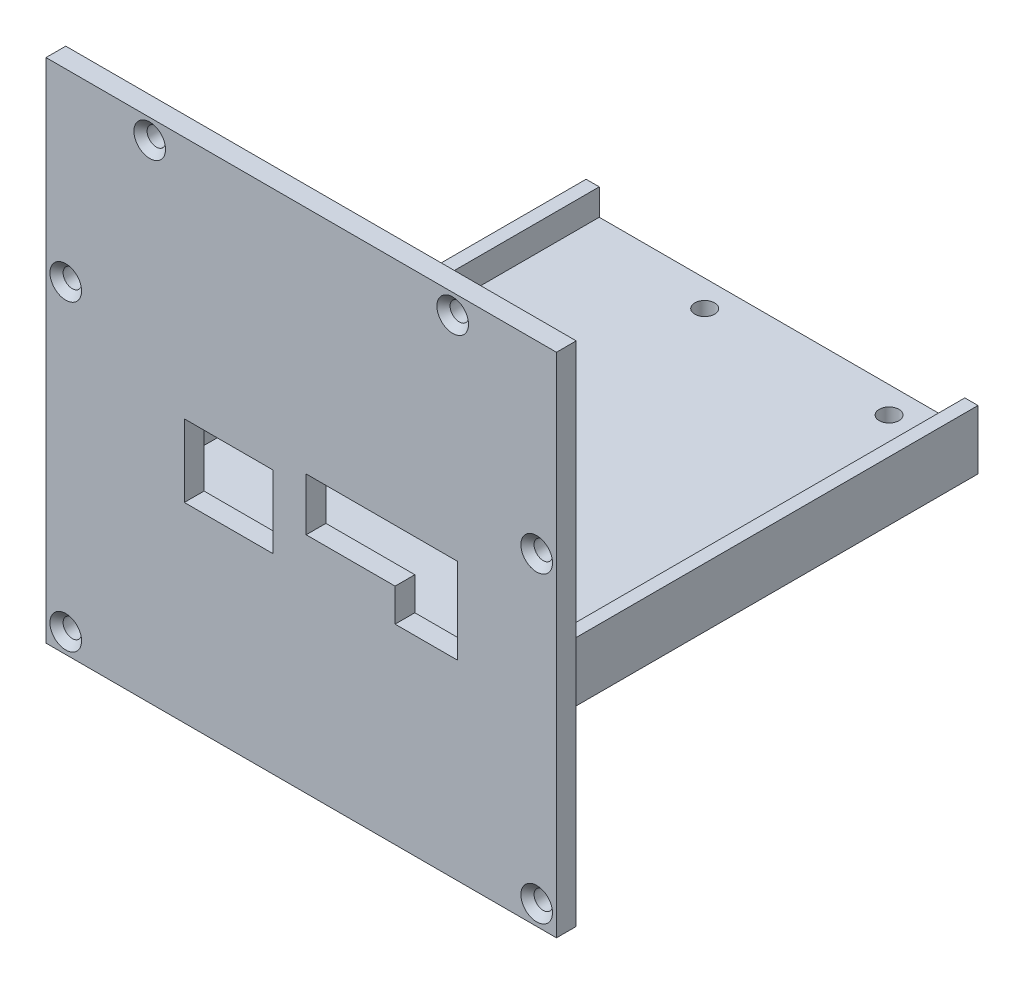
SolidWorks part; units mm, degrees
ref_plane "Płaszczyzna przednia" through (0, 0, 0) normal (0, 0, 1) x (1, 0, 0)
ref_plane "Płaszczyzna górna" through (0, 0, 0) normal (0, 1, 0) x (1, 0, 0)
ref_plane "Płaszczyzna prawa" through (0, 0, 0) normal (1, 0, 0) x (0, 0, -1)
sketch "Szkic1" plane through (0, 0, 0) normal (0, 0, 1) x (1, 0, 0)
  line L0 (14.6708, -41.7555) -> (14.6708, -118.7555) construction
  line L1 (-3.0792, -78.7555) -> (10.4208, -78.7555)
  line L2 (-3.0792, -78.7555) -> (-3.0792, -89.7555)
  line L3 (-3.0792, -89.7555) -> (10.4208, -89.7555)
  line L4 (-24.0792, -118.7555) -> (53.4208, -118.7555)
  line L5 (53.4208, -118.7555) -> (53.4208, -41.7555)
  line L6 (53.4208, -41.7555) -> (-24.0792, -41.7555)
  line L7 (-24.0792, -41.7555) -> (-24.0792, -118.7555)
  line L8 (10.4208, -78.7555) -> (10.4208, -89.7555)
  line L9 (29.4208, -76.7555) -> (38.4208, -76.7555)
  line L10 (28.9208, -84.7555) -> (28.9208, -89.7555)
  line L11 (28.9208, -89.7555) -> (38.4208, -89.7555)
  line L12 (38.4208, -76.7555) -> (38.4208, -89.7555)
  line L13 (-13.0792, -93.7555) -> (42.4208, -93.7555)
  line L14 (-13.0792, -93.7555) -> (-13.0792, -89.7555)
  line L15 (42.4208, -89.7555) -> (42.4208, -93.7555)
  line L16 (-15.0792, -98.7555) -> (-15.0792, -89.7555)
  line L17 (-15.0792, -98.7555) -> (44.4208, -98.7555)
  line L18 (44.4208, -89.7555) -> (44.4208, -98.7555)
  line L19 (-13.0792, -89.7555) -> (-15.0792, -89.7555)
  line L20 (42.4208, -89.7555) -> (44.4208, -89.7555)
  line L21 (-3.0792, -84.2555) -> (-50.0911, -84.2555) construction
  line L22 (-50.0911, -84.2555) -> (82.1697, -84.2555) construction
  line L24 (15.4208, -76.7555) -> (29.4208, -76.7555)
  line L25 (15.4208, -76.7555) -> (15.4208, -91.7555)
  line L29 (15.4208, -91.7555) -> (15.4208, -84.7555)
  line L30 (15.4208, -84.7555) -> (28.9208, -84.7555)
  line L31 (15.4208, -76.7555) -> (15.4208, -91.7555)
  line L33 (38.4208, -91.7555) -> (38.4208, -76.7555)
  dimension "D12" = 4
  dimension "D1" = 9
  dimension "D2" = 13.5
  dimension "D3" = 13
  dimension "D4" = 5
  dimension "D5" = 10
  dimension "D6" = 23
  dimension "D7" = 20
  dimension "D8" = 11
  dimension "D9" = 5
  dimension "D10" = 2
  dimension "D11" = 15
  dimension "D15" = 5
  dimension "D16" = 21
  dimension "D17" = 77
  dimension "D18" = 77.5
extrude "Dodanie-wyciągnięcie1" add sketch "Szkic1" along normal blind 3 contours L4 L1 L3 L9 L12 L11 L15 L20 L18 L17 L16 L19 L14 | L17 L18 L20 L15 L13 L14 L19 L16 region at (14.3821, -79.125, 0)
extrude "Dodanie-wyciągnięcie3" add sketch "Szkic1<5>" against normal blind 70 contours L20 L15 L13 L14 L19 L16 L17 L18 region at (14.6708, -96.0259, 0)
sketch "Szkic1<5>" plane through (0, 0, 0) normal (0, 0, 1) x (1, 0, 0) same geometry as "Szkic1"
sketch "Szkic2" plane through (0, 0, 3) normal (0, 0, 1) x (1, 0, 0)
  line L0 (-11.3292, -41.7555) -> (-5.3292, -41.7555)
  line L1 (-11.3292, -47.7555) -> (-5.3292, -47.7555)
  line L2 (-5.3292, -47.7555) -> (-5.3292, -41.7555)
  line L3 (14.6708, -70.3917) -> (14.6708, -64.3917) construction
  line L4 (-11.3292, -41.7555) -> (-5.3292, -41.7555)
  line L5 (-11.3292, -41.7555) -> (-11.3292, -47.7555)
  line L6 (40.6708, -41.7555) -> (40.6708, -47.7555)
  line L7 (40.6708, -47.7555) -> (34.6708, -47.7555)
  line L8 (34.6708, -47.7555) -> (34.6708, -41.7555)
  line L9 (40.6708, -41.7555) -> (34.6708, -41.7555)
  line L10 (-24.0792, -41.7555) -> (-24.0792, -118.7555) construction
  line L11 (53.4208, -118.7555) -> (53.4208, -41.7555) construction
  line L12 (53.4208, -41.7555) -> (-24.0792, -41.7555) construction
  circle A0 centre (-8.3292, -44.7555) radius 1.4
  circle A1 centre (37.6708, -44.7555) radius 1.4
  dimension "D1" = 2.8
  dimension "D2" = 3
  dimension "D3" = 3
  dimension "D4" = 3
  dimension "D5" = 20
extrude "Wytnij-wyciągnięcie1" cut sketch "Szkic2" against normal up to surface (3 mm away) contours A0 | A1 region at (-8.3292, -44.7555, 3) region at (37.6708, -44.7555, 3) up to face at (3.6708, -84.2555, 0)
sketch "Szkic3" plane through (0, 0, 0) normal (0, 0, -1) x (-1, 0, 0)
  line L0 (-53.4208, -66.7555) -> (-47.4208, -66.7555)
  line L1 (-53.4208, -72.7555) -> (-47.4208, -72.7555)
  line L2 (-47.4208, -72.7555) -> (-47.4208, -66.7555)
  line L3 (-14.6708, -61.974) -> (-14.6708, -55.974) construction
  line L4 (-53.4208, -66.7555) -> (-47.4208, -66.7555)
  line L5 (-53.4208, -66.7555) -> (-53.4208, -72.7555)
  line L6 (24.0792, -66.7555) -> (24.0792, -72.7555)
  line L7 (24.0792, -72.7555) -> (18.0792, -72.7555)
  line L8 (18.0792, -72.7555) -> (18.0792, -66.7555)
  line L9 (24.0792, -66.7555) -> (18.0792, -66.7555)
  line L10 (-53.4208, -112.7555) -> (-47.4208, -112.7555)
  line L11 (-53.4208, -118.7555) -> (-47.4208, -118.7555)
  line L12 (-47.4208, -118.7555) -> (-47.4208, -112.7555)
  line L13 (-14.6708, -81.1098) -> (-14.6708, -75.1098) construction
  line L14 (-53.4208, -112.7555) -> (-47.4208, -112.7555)
  line L15 (-53.4208, -112.7555) -> (-53.4208, -118.7555)
  line L16 (24.0792, -112.7555) -> (24.0792, -118.7555)
  line L17 (24.0792, -118.7555) -> (18.0792, -118.7555)
  line L18 (18.0792, -118.7555) -> (18.0792, -112.7555)
  line L19 (24.0792, -112.7555) -> (18.0792, -112.7555)
  line L20 (-53.4208, -118.7555) -> (-53.4208, -41.7555) construction
  line L21 (24.0792, -41.7555) -> (24.0792, -118.7555) construction
  line L22 (24.0792, -118.7555) -> (-53.4208, -118.7555) construction
  circle A0 centre (-50.4208, -69.7555) radius 1.4
  circle A1 centre (21.0792, -69.7555) radius 1.4
  circle A2 centre (-50.4208, -115.7555) radius 1.4
  circle A3 centre (21.0792, -115.7555) radius 1.4
  dimension "D1" = 2.8
  dimension "D6" = 2.8
  dimension "D2" = 3
  dimension "D3" = 3
  dimension "D4" = 3
  dimension "D5" = 40
  dimension "D7" = 3
  dimension "D8" = 3
  dimension "D9" = 3
sketch "Szkic4" plane through (0, 0, 3) normal (0, 0, 1) x (1, 0, 0)
  line L0 (53.4208, -66.7555) -> (47.4208, -66.7555) construction
  line L1 (47.4208, -72.7555) -> (47.4208, -66.7555) construction
  line L2 (53.4208, -72.7555) -> (47.4208, -72.7555) construction
  line L3 (53.4208, -66.7555) -> (53.4208, -72.7555) construction
  line L4 (-24.0792, -66.7555) -> (-24.0792, -72.7555)
  line L5 (-24.0792, -72.7555) -> (-18.0792, -72.7555)
  line L6 (-18.0792, -72.7555) -> (-18.0792, -66.7555)
  line L7 (-18.0792, -66.7555) -> (-24.0792, -66.7555)
  line L8 (-24.0792, -66.7555) -> (-24.0792, -72.7555)
  line L9 (-24.0792, -72.7555) -> (-18.0792, -72.7555)
  line L10 (-18.0792, -72.7555) -> (-18.0792, -66.7555)
  line L11 (-18.0792, -66.7555) -> (-24.0792, -66.7555)
  line L12 (-24.0792, -112.7555) -> (-24.0792, -118.7555)
  line L13 (-24.0792, -118.7555) -> (-18.0792, -118.7555)
  line L14 (-18.0792, -118.7555) -> (-18.0792, -112.7555)
  line L15 (-18.0792, -112.7555) -> (-24.0792, -112.7555)
  line L16 (-24.0792, -112.7555) -> (-24.0792, -118.7555)
  line L17 (-24.0792, -118.7555) -> (-18.0792, -118.7555)
  line L18 (-18.0792, -118.7555) -> (-18.0792, -112.7555)
  line L19 (-18.0792, -112.7555) -> (-24.0792, -112.7555)
  line L20 (53.4208, -66.7555) -> (47.4208, -66.7555) construction
  line L21 (53.4208, -112.7555) -> (47.4208, -112.7555) construction
  line L22 (47.4208, -118.7555) -> (47.4208, -112.7555) construction
  line L23 (53.4208, -118.7555) -> (47.4208, -118.7555) construction
  line L24 (53.4208, -112.7555) -> (53.4208, -118.7555) construction
  line L25 (53.4208, -112.7555) -> (47.4208, -112.7555) construction
  line L26 (53.4208, -66.7555) -> (47.4208, -66.7555)
  line L27 (47.4208, -72.7555) -> (47.4208, -66.7555)
  line L28 (53.4208, -72.7555) -> (47.4208, -72.7555)
  line L29 (53.4208, -66.7555) -> (53.4208, -72.7555)
  line L30 (53.4208, -66.7555) -> (47.4208, -66.7555)
  line L31 (53.4208, -112.7555) -> (47.4208, -112.7555)
  line L32 (47.4208, -118.7555) -> (47.4208, -112.7555)
  line L33 (53.4208, -118.7555) -> (47.4208, -118.7555)
  line L34 (53.4208, -112.7555) -> (53.4208, -118.7555)
  line L35 (53.4208, -112.7555) -> (47.4208, -112.7555)
  circle A1 centre (50.4208, -115.7555) radius 1.4
  circle A2 centre (50.4208, -115.7555) radius 1.4
  circle A3 centre (-21.0792, -69.7555) radius 1.4
  circle A4 centre (-21.0792, -69.7555) radius 1.4
  circle A5 centre (50.4208, -69.7555) radius 1.4
  circle A6 centre (50.4208, -69.7555) radius 1.4
  circle A7 centre (-21.0792, -115.7555) radius 1.4
  circle A8 centre (-21.0792, -115.7555) radius 1.4
  dimension "D1" = 0
  dimension "D2" = 0
  dimension "D3" = 0
  dimension "D4" = 0
  dimension "D5" = 0
  dimension "D6" = 0
extrude "Wytnij-wyciągnięcie2" cut sketch "Szkic4" against normal up to surface (3 mm away) contours A4 | A8 | A2 | A6 region at (50.4208, -115.7555, 3) region at (-21.0792, -69.7555, 3) region at (-21.0792, -115.7555, 3) up to face at (14.6708, -93.0055, 0)
sketch "Szkic5" plane through (0, -93.7555, 0) normal (0, 1, 0) x (1, 0, 0)
  line L4 (-13.0792, 0) -> (42.4208, 0)
  line L5 (42.4208, 0) -> (42.4208, 70)
  line L6 (42.4208, 70) -> (-13.0792, 70)
  line L7 (-13.0792, 70) -> (-13.0792, 0)
  line L8 (-13.0792, 0) -> (42.4208, 0)
  line L9 (42.4208, 0) -> (42.4208, 70)
  line L10 (42.4208, 70) -> (-13.0792, 70)
  line L11 (-13.0792, 70) -> (-13.0792, 0)
  circle A0 centre (6.9208, 66) radius 1.5
  circle A1 centre (34.9208, 66) radius 1.5
  dimension "D2" = 3
  dimension "D3" = 4
  dimension "D4" = 7.5
  dimension "D5" = 28
  dimension "D1" = 0
extrude "Wytnij-wyciągnięcie3" cut sketch "Szkic5" against normal up to surface (5 mm away) contours A1 | A0 region at (34.9208, -93.7555, -66) up to face at (14.6708, -98.7555, -35)
chamfer "Sfazowanie1" distance 1 angle 45 1 edges at (-6.9292, -44.7555, 3)
chamfer "Sfazowanie2" distance 1 angle 45 1 edges at (39.0708, -44.7555, 3)
chamfer "Sfazowanie3" distance 1 angle 45 4 edges at (51.8208, -115.7555, 3) (-19.6792, -115.7555, 3) (51.8208, -69.7555, 3) (-19.6792, -69.7555, 3)
